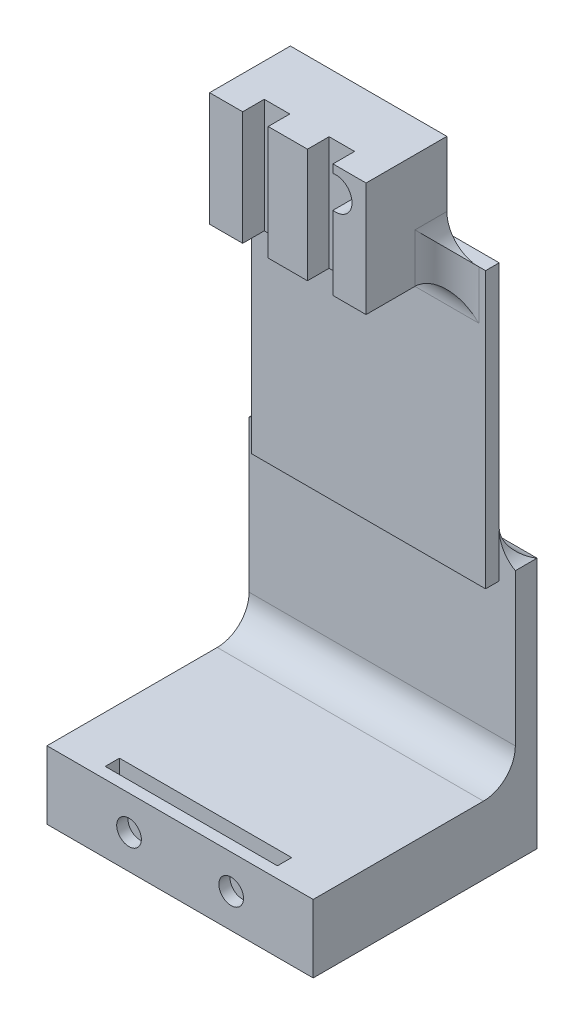
SolidWorks part; units mm, degrees
ref_plane "Front Plane" through (0, 0, 0) normal (0, 0, 1) x (1, 0, 0)
ref_plane "Top Plane" through (0, 0, 0) normal (0, 1, 0) x (1, 0, 0)
ref_plane "Right Plane" through (0, 0, 0) normal (1, 0, 0) x (0, 0, -1)
sketch "Sketch1" plane through (0, 0, 0) normal (0, 0, 1) x (1, 0, 0)
  line L1 (0, 0) -> (-27.5, 0)
  line L2 (0, 0) -> (0, 32.4)
  line L3 (0, 32.4) -> (-27.5, 32.4)
  line L4 (-27.5, 0) -> (-27.5, 32.4)
  dimension "D1" = 27.5
  dimension "D2" = 32.4
extrude "Boss-Extrude1" add sketch "Sketch1" along normal blind 1.6
sketch "Sketch2" plane through (0, 0, 1.6) normal (0, 0, 1) x (1, 0, 0)
  line L0 (0, 32.4) -> (-27.5, 32.4) construction
  line L1 (-22.95, 30.4) -> (-4.55, 30.4)
  line L2 (-22.95, 30.4) -> (-22.95, 43.8)
  line L3 (-22.95, 43.8) -> (-4.55, 43.8)
  line L4 (-4.55, 30.4) -> (-4.55, 43.8)
  line L5 (-27.5, 0) -> (0, 0) construction
  point P8 (-13.75, 0)
  point P9 (-13.75, 30.4)
  dimension "D1" = 13.4
  dimension "D2" = 2
  dimension "D3" = 0
  dimension "D4" = 18.4
extrude "Boss-Extrude2" add sketch "Sketch2" along normal blind 9.5
sketch "Sketch3" plane through (0, 0, 0) normal (0, 0, -1) x (-1, 0, 0)
  line L0 (27.5, 0) -> (0, 0) construction
  line L1 (-1.9, 2) -> (29.4, 2)
  line L2 (-1.9, 2) -> (-1.9, -17.46)
  line L3 (-1.9, -17.46) -> (29.4, -17.46)
  line L4 (29.4, 2) -> (29.4, -17.46)
  point P6 (13.75, 0)
  point P7 (13.75, -17.46)
  dimension "D1" = 19.46
  dimension "D2" = 2
  dimension "D3" = 31.3
  dimension "D4" = 0
extrude "Boss-Extrude3" add sketch "Sketch3" along normal blind 2.55
sketch "Sketch5" plane through (0, 0, -2.55) normal (0, 0, -1) x (-1, 0, 0)
  line L0 (-1.9, -15.66) -> (29.4, -15.66) construction
  line L1 (-1.9, 2) -> (-1.9, -17.46) construction
  line L2 (29.4, -17.46) -> (29.4, 2) construction
  line L3 (-1.9, -17.46) -> (29.4, -17.46) construction
  dimension "D1" = 1.8
sketch "Sketch6" plane through (0, 0, 11.1) normal (0, 0, 1) x (1, 0, 0)
  line L0 (-17.56, 43.8) -> (-17.56, 30.4) construction
  line L1 (-4.55, 43.8) -> (-22.95, 43.8) construction
  line L2 (-22.95, 30.4) -> (-4.55, 30.4) construction
  line L3 (-9.94, 43.8) -> (-9.94, 30.4) construction
  line L4 (-22.95, 30.4) -> (-4.55, 30.4) construction
  line L5 (-19.06, 43.8) -> (-19.06, 30.4)
  line L6 (-16.06, 43.8) -> (-16.06, 30.4)
  line L7 (-11.44, 43.8) -> (-11.44, 30.4)
  line L8 (-8.44, 43.8) -> (-8.44, 30.4)
  line L9 (-13.75, 43.8) -> (-13.75, 30.4) construction
  line L10 (-17.56, 37.1) -> (-13.75, 37.1) construction
  line L11 (-9.94, 37.1) -> (-13.75, 37.1) construction
  line L12 (-19.06, 43.8) -> (-16.06, 43.8)
  line L13 (-19.06, 30.4) -> (-16.06, 30.4)
  line L14 (-11.44, 43.8) -> (-8.44, 43.8)
  line L15 (-11.44, 30.4) -> (-8.44, 30.4)
  dimension "D1" = 7.62
  dimension "D2" = 1.5
  dimension "D3" = 1.5
  dimension "D4" = 1.5
  dimension "D5" = 1.5
extrude "Cut-Extrude1" cut sketch "Sketch6" against normal blind 2.54
sketch "Sketch7" plane through (0, 0, 11.1) normal (0, 0, 1) x (1, 0, 0)
  line L0 (-8.106, 43.8) -> (-8.106, 30.4) construction
  line L1 (-4.55, 43.8) -> (-8.44, 43.8) construction
  line L2 (-22.95, 30.4) -> (-4.55, 30.4) construction
  line L3 (-4.55, 30.4) -> (-4.55, 43.8) construction
  line L4 (-22.95, 40.9552) -> (-4.55, 40.9552) construction
  line L5 (-22.95, 43.8) -> (-22.95, 30.4) construction
  line L6 (-8.106, 43.8) -> (-8.106, 30.4)
  line L7 (-22.95, 40.9552) -> (-4.55, 40.9552)
  circle A0 centre (-8.106, 40.9552) radius 1.905
  line M6 (-8.44, 43.8) -> (-8.44, 30.4)
  dimension "D4" = 3.81
  dimension "D1" = 3.556
  dimension "D2" = 2.8448
  dimension "D3" = 0
extrude "Cut-Extrude2" cut sketch "Sketch7" against normal up to surface (2.54 mm away) contours A0 L7 M6 | L7 A0 L6 | L6 A0 L7 | L7 A0 M6 | L6 A0 L7 M6 | A0 L6 L7 M6 region at (-7.2975, 41.7637, 11.1) region at (-8.2726, 41.9028, 11.1) region at (-7.2975, 40.1467, 11.1) region at (-8.2726, 40.0076, 11.1) region at (-9.0978, 41.724, 11.1) region at (-9.0978, 40.1864, 11.1) up to face at (-9.94, 37.1, 8.56)
sketch "Sketch9" plane through (0, -17.46, 0) normal (0, -1, 0) x (1, 0, 0)
  line L1 (-29.4, -2.55) -> (1.9, -2.55)
  line L2 (-29.4, -2.55) -> (-29.4, 0)
  line L3 (-29.4, 0) -> (1.9, 0)
  line L4 (1.9, -2.55) -> (1.9, 0)
extrude "Boss-Extrude4" add sketch "Sketch9" along normal blind 2.132
sketch "Sketch11" plane through (0, -19.592, 0) normal (0, -1, 0) x (1, 0, 0)
  line L0 (1.9, -2.55) -> (1.9, 0) construction
  line L1 (-29.4, -2.55) -> (1.9, -2.55)
  line L2 (-29.4, -2.55) -> (-29.4, 23.7672)
  line L3 (-29.4, 23.7672) -> (1.9, 23.7672)
  line L4 (1.9, -2.55) -> (1.9, 23.7672)
  dimension "D1" = 0
  dimension "D2" = 26.3172
extrude "Boss-Extrude5" add sketch "Sketch11" along normal blind 8
sketch "Sketch12" plane through (0, -27.592, 0) normal (0, -1, 0) x (1, 0, 0)
  line L0 (1.9, 10.6086) -> (-29.4, 10.6086) construction
  line L1 (-23.875, 20.77) -> (-3.625, 20.77)
  line L2 (-23.875, 20.77) -> (-23.875, 22.448)
  line L3 (-23.875, 22.448) -> (-3.625, 22.448)
  line L4 (-3.625, 20.77) -> (-3.625, 22.448)
  line L5 (1.9, -2.55) -> (1.9, 23.7672) construction
  line L6 (-29.4, 23.7672) -> (-29.4, -2.55) construction
  line L7 (-13.75, 23.7672) -> (-13.75, -2.55) construction
  line L8 (1.9, 23.7672) -> (-29.4, 23.7672) construction
  line L9 (1.9, -2.55) -> (-29.4, -2.55) construction
  line L10 (-29.4, -2.55) -> (1.9, -2.55) construction
  point P16 (-13.75, 22.448)
  dimension "D1" = 1.678
  dimension "D2" = 20.25
  dimension "D3" = 0
  dimension "D4" = 23.32
extrude "Cut-Extrude3" cut sketch "Sketch12" against normal blind 8
fillet "Fillet1" radius 0.5 4 edges at (-3.625, -27.592, 21.609) (-13.75, -27.592, 22.448) (-23.875, -27.592, 21.609) (-13.75, -27.592, 20.77)
sketch "Sketch13" plane through (0, 0, 23.7672) normal (0, 0, 1) x (1, 0, 0)
  line L3 (-13.75, -19.592) -> (-13.75, -27.592) construction
  line L4 (1.9, -19.592) -> (-29.4, -19.592) construction
  line L5 (1.9, -27.592) -> (-29.4, -27.592) construction
  line L6 (-19.7549, -23.592) -> (-13.75, -27.592) construction
  line L7 (-7.7451, -23.592) -> (-13.75, -27.592) construction
  line L8 (-21.2049, -23.592) -> (-21.2049, -19.592) construction
  line L9 (1.9, -19.592) -> (-29.4, -19.592) construction
  line L10 (-6.2951, -23.592) -> (-6.2951, -19.592) construction
  line L11 (-29.4, -23.592) -> (1.9, -23.592) construction
  line L12 (-29.4, -27.592) -> (-29.4, -19.592) construction
  line L13 (1.9, -27.592) -> (1.9, -19.592) construction
  circle A0 centre (-19.7549, -23.592) radius 1.45
  circle A1 centre (-7.7451, -23.592) radius 1.45
  dimension "D1" = 2.9
  dimension "D3" = 0
  dimension "D2" = 0
  dimension "D4" = 14.9098
extrude "Cut-Extrude4" cut sketch "Sketch13" against normal blind 6
fillet "Fillet2" radius 3.75 1 edges at (-13.75, -19.592, 0)
fillet "Fillet3" radius 3.75 1 edges at (-13.75, 2, 0)
fillet "Fillet4" radius 3.75 1 edges at (-13.75, 30.4, 1.6)
fillet "Fillet5" radius 3.75 1 edges at (-22.95, 29.525, 1.6)
fillet "Fillet6" radius 3.75 1 edges at (-4.55, 29.525, 1.6)
fillet "Fillet7" radius 3.75 1 edges at (-22.95, 32.4, 3.475)
fillet "Fillet8" radius 3.75 1 edges at (-4.55, 32.4, 3.475)
fillet "Fillet9" radius 3.75 2 edges at (0, 2, -1.275) (-27.5, 2, -1.275)
